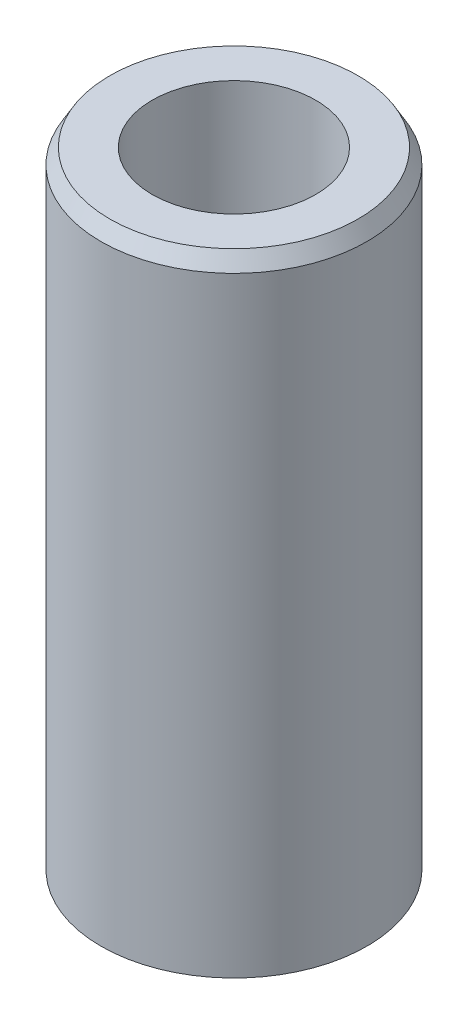
SolidWorks part; units mm, degrees
ref_plane "Front Plane" through (0, 0, 0) normal (0, 0, 1) x (1, 0, 0)
ref_plane "Top Plane" through (0, 0, 0) normal (0, 1, 0) x (1, 0, 0)
ref_plane "Right Plane" through (0, 0, 0) normal (1, 0, 0) x (0, 0, -1)
sketch "Sketch1" plane through (0, 0, 0) normal (0, 1, 0) x (1, 0, 0)
  circle A0 centre (0, 0) radius 12.5
  dimension "SHAFT_OD" = 25
extrude "Boss-Extrude1" add sketch "Sketch1" along normal blind 59.6295
sketch "Sketch2" plane through (0, 0, 0) normal (0, 1, 0) x (1, 0, 0)
  circle A0 centre (0, 0) radius 7.6886
  dimension "BORE_D" = 15.3772
extrude "Cut-Extrude1" cut sketch "Sketch2" along normal through all
chamfer "Chamfer1" distance 1.427 angle 30 2 edges at (0, 59.6295, 12.5) (0, 0, 12.5) first distance on face at (0, 59.6295, 12.5) first distance on face at (0, 0, 7.6886)
